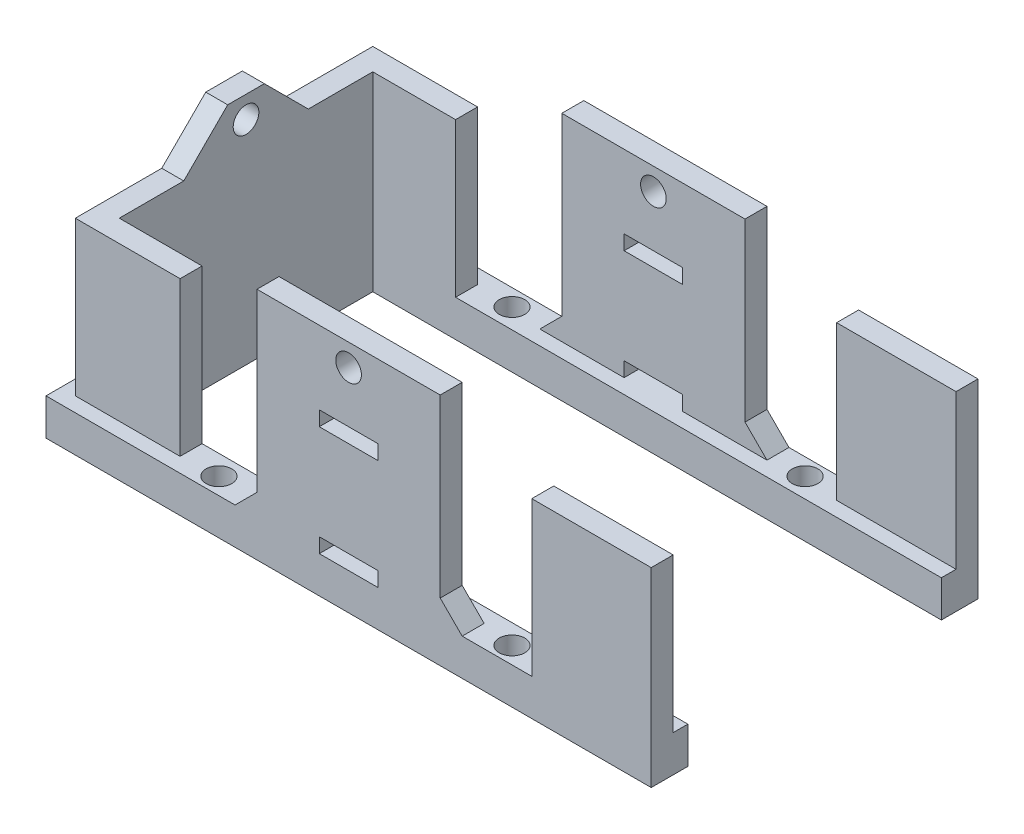
SolidWorks part; units mm, degrees
material "PP Copolymer"
ref_plane "Alzado" through (0, 0, 0) normal (0, 0, 1) x (1, 0, 0)
ref_plane "Planta" through (0, 0, 0) normal (0, 1, 0) x (1, 0, 0)
ref_plane "Vista lateral" through (0, 0, 0) normal (1, 0, 0) x (0, 0, -1)
sketch "Croquis1" plane through (0, 0, 0) normal (0, 1, 0) x (1, 0, 0)
  line L0 (-20, 20) -> (-20, -20) construction
  line L1 (-36, 17) -> (36, 17) construction
  line L2 (-36, 17) -> (-36, -17) construction
  line L3 (-36, -17) -> (36, -17) construction
  line L4 (36, 17) -> (36, -17) construction
  line L5 (-36, 17) -> (36, -17) construction
  line L6 (-36, -17) -> (36, 17) construction
  line L7 (-20, -20) -> (20, -20) construction
  line L8 (20, -20) -> (20, 20) construction
  line L9 (20, 20) -> (-20, 20) construction
  line L10 (-20, 0) -> (0, 0) construction
  line L11 (0, 0) -> (0, 20) construction
  line L12 (-36.3, 17.3) -> (36.3, 17.3)
  line L13 (36.3, 17.3) -> (36.3, -17.3) construction
  line L14 (-36.3, -17.3) -> (36.3, -17.3)
  line L15 (-36.3, 17.3) -> (-36.3, -17.3)
  line L16 (-41.3, 22.3) -> (-41.3, -22.3)
  line L17 (-41.3, -22.3) -> (41.3, -22.3)
  line L18 (41.3, 22.3) -> (41.3, -22.3) construction
  line L19 (-41.3, 22.3) -> (41.3, 22.3)
  line L20 (36.3, 17.3) -> (41.3, 17.3)
  line L21 (41.3, -17.3) -> (36.3, -17.3)
  line L22 (41.3, 17.3) -> (41.3, 22.3)
  line L23 (41.3, -17.3) -> (41.3, -22.3)
  circle A0 centre (-20, 20) radius 1.75
  circle A1 centre (20, 20) radius 1.75
  circle A2 centre (-20, -20) radius 1.75
  circle A3 centre (20, -20) radius 1.75
  point P0 (0, 0)
  dimension "D3" = 3.5
  dimension "D4" = 40
  dimension "D1" = 72
  dimension "D2" = 34
  dimension "D5" = 0.3
  dimension "D6" = 5
  dimension "D7" = 77.6
extrude "Saliente-Extruir1" add sketch "Croquis1" along normal blind 5
sketch "Croquis2" plane through (0, 5, 0) normal (0, 1, 0) x (1, 0, 0)
  line L2 (-39.3, 20.3) -> (-39.3, -20.3)
  line L4 (-36.3, 17.3) -> (-36.3, -17.3)
  line L5 (-36.3, -17.3) -> (-36.3, 17.3) construction
  line L6 (41.3, -17.3) -> (-36.3, -17.3) construction
  line L7 (-12.5, -19.3) -> (12.5, -19.3)
  line L8 (-12.5, -19.3) -> (-12.5, -22.3)
  line L9 (-12.5, -22.3) -> (12.5, -22.3)
  line L10 (12.5, -19.3) -> (12.5, -22.3)
  line L13 (-12.5, 22.3) -> (12.5, 22.3)
  line L14 (-12.5, 22.3) -> (-12.5, 19.3)
  line L15 (-12.5, 19.3) -> (12.5, 19.3)
  line L16 (12.5, 22.3) -> (12.5, 19.3)
  line L17 (-36.3, 17.3) -> (41.3, 17.3) construction
  line L18 (0, 19.3) -> (0, -19.3) construction
  line L19 (-36.3, 0) -> (0, 0) construction
  line L20 (-39.3, -20.3) -> (-25, -20.3)
  line L21 (41.3, -19.3) -> (25, -19.3)
  line L22 (41.3, -19.3) -> (41.3, -22.3)
  line L23 (41.3, -22.3) -> (25, -22.3)
  line L24 (25, -19.3) -> (25, -22.3)
  line L25 (41.3, 22.3) -> (25, 22.3)
  line L26 (41.3, 22.3) -> (41.3, 19.3)
  line L27 (41.3, 19.3) -> (25, 19.3)
  line L28 (25, 22.3) -> (25, 19.3)
  line L29 (-25, -20.3) -> (-25, -17.3)
  line L30 (-25, -17.3) -> (-36.3, -17.3)
  line L31 (-36.3, 17.3) -> (-25, 17.3)
  line L32 (-25, 17.3) -> (-25, 20.3)
  line L33 (-25, 20.3) -> (-39.3, 20.3)
  line L34 (41.3, 17.3) -> (41.3, 22.3) construction
  line L35 (-25, 20.3) -> (-25, 22.3) construction
  line L36 (41.3, 22.3) -> (-41.3, 22.3) construction
  line L37 (-25, 22.3) -> (-12.5, 22.3) construction
  line L46 (-41.3, -22.3) -> (41.3, -22.3) construction
  line L52 (-25, -22.3) -> (-25, -20.3) construction
  circle A0 centre (20, -20) radius 1.75 construction
  circle A2 centre (-20, 20) radius 1.75 construction
  point P4 (0, 0)
  point P5 (0, 0)
  point P14 (0, 0)
  point P19 (0, 0)
  point P21 (39.8653, -22.3)
  point P40 (0, 0)
  point P43 (0, 0)
  point P45 (0, 0)
  point P51 (0, 0)
  dimension "D2" = 5
  dimension "D1" = 25
  dimension "D3" = 5
  dimension "D4" = 3
  dimension "D5" = 3
extrude "Saliente-Extruir2" add sketch "Croquis2" along normal blind 21
sketch "Croquis3" plane through (0, 26, 0) normal (0, 1, 0) x (1, 0, 0)
  line L0 (-20, -20) -> (-20, 20) construction
  line L1 (-20, 20) -> (20, 20) construction
  line L2 (20, 20) -> (20, -20) construction
  line L3 (20, -20) -> (-20, -20) construction
  line L4 (-20, 0) -> (0, 0) construction
  line L5 (0, 0) -> (0, 20) construction
  circle A0 centre (-20, 20) radius 1.75
  circle A1 centre (20, 20) radius 1.75
  circle A2 centre (20, -20) radius 1.75
  circle A3 centre (-20, -20) radius 1.75
  dimension "D1" = 40
  dimension "D3" = 3.5
  dimension "D2" = 40
extrude "Cortar-Extruir1" [suppressed] cut sketch "Croquis3" against normal through all
sketch "Croquis4" plane through (0, 26, 0) normal (0, 1, 0) x (1, 0, 0)
  line L0 (-36.3, -17.3) -> (-36.3, 17.3) construction
  line L1 (-39.3, -2.5) -> (-36.3, -2.5)
  line L2 (-39.3, -2.5) -> (-39.3, 2.5)
  line L3 (-39.3, 2.5) -> (-36.3, 2.5)
  line L4 (-36.3, -2.5) -> (-36.3, 2.5)
  line L5 (-39.3, -2.5) -> (-36.3, 2.5) construction
  line L6 (-39.3, 2.5) -> (-36.3, -2.5) construction
  line L7 (-39.3, 20.3) -> (-39.3, -20.3) construction
  point P0 (-37.8, 0)
  dimension "D1" = 5
extrude "Saliente-Extruir3" add sketch "Croquis4" along normal blind 6
sketch "Croquis5" plane through (-39.3, 0, 0) normal (-1, 0, 0) x (0, 0, 1)
  line L0 (-2.5, 32) -> (2.5, 32) construction
  circle A0 centre (0, 29) radius 1.75
  dimension "D1" = 3.5
  dimension "D2" = 3
extrude "Cortar-Extruir2" cut sketch "Croquis5" against normal through all
chamfer "Chaflán1" distance 6 angle 45 2 edges at (-37.8, 26, 2.5) (-37.8, 26, -2.5)
sketch "Croquis6" plane through (0, 26, 0) normal (0, 1, 0) x (1, 0, 0)
  line L0 (-12.5, 22.3) -> (-12.5, 19.3) construction
  line L1 (-12.5, 19.3) -> (12.5, 19.3) construction
  line L2 (12.5, 19.3) -> (12.5, 22.3) construction
  line L3 (12.5, 22.3) -> (-12.5, 22.3) construction
  line L4 (-12.5, -19.3) -> (-12.5, -22.3) construction
  line L5 (-12.5, -22.3) -> (12.5, -22.3) construction
  line L6 (12.5, -22.3) -> (12.5, -19.3) construction
  line L7 (12.5, -19.3) -> (-12.5, -19.3) construction
  line L8 (-12.5, 22.3) -> (-12.5, 19.3)
  line L9 (-12.5, 19.3) -> (12.5, 19.3)
  line L10 (12.5, 19.3) -> (12.5, 22.3)
  line L11 (12.5, 22.3) -> (-12.5, 22.3)
  line L12 (-12.5, -19.3) -> (-12.5, -22.3)
  line L13 (-12.5, -22.3) -> (12.5, -22.3)
  line L14 (12.5, -22.3) -> (12.5, -19.3)
  line L15 (12.5, -19.3) -> (-12.5, -19.3)
extrude "Saliente-Extruir4" add sketch "Croquis6" along normal blind 6
sketch "Croquis7" plane through (0, 0, -22.3) normal (0, 0, -1) x (-1, 0, 0)
  line L0 (12.5, 5) -> (41.3, 5) construction
  line L1 (-4, 22) -> (4, 22)
  line L2 (-4, 22) -> (-4, 20)
  line L3 (-4, 20) -> (4, 20)
  line L4 (4, 22) -> (4, 20)
  line L5 (-4, 22) -> (4, 20) construction
  line L6 (-4, 20) -> (4, 22) construction
  line L7 (-4, 7) -> (4, 7)
  line L8 (-4, 7) -> (-4, 5)
  line L9 (-4, 5) -> (4, 5)
  line L10 (4, 7) -> (4, 5)
  line L11 (-4, 7) -> (4, 5) construction
  line L12 (-4, 5) -> (4, 7) construction
  line L13 (-12.5, 32) -> (12.5, 32) construction
  circle A0 centre (0, 29) radius 1.75
  point P0 (0, 21)
  point P5 (0, 6)
  point P17 (0, 0)
  dimension "D4" = 3.5
  dimension "D1" = 2
  dimension "D2" = 8
  dimension "D3" = 15
  dimension "D5" = 3
extrude "Cortar-Extruir3" cut sketch "Croquis7" against normal through all
chamfer "Chaflán2" distance 3 angle 45 4 edges at (-12.5, 5, 20.8) (12.5, 5, 20.8) (-12.5, 5, -20.8) (12.5, 5, -20.8)
